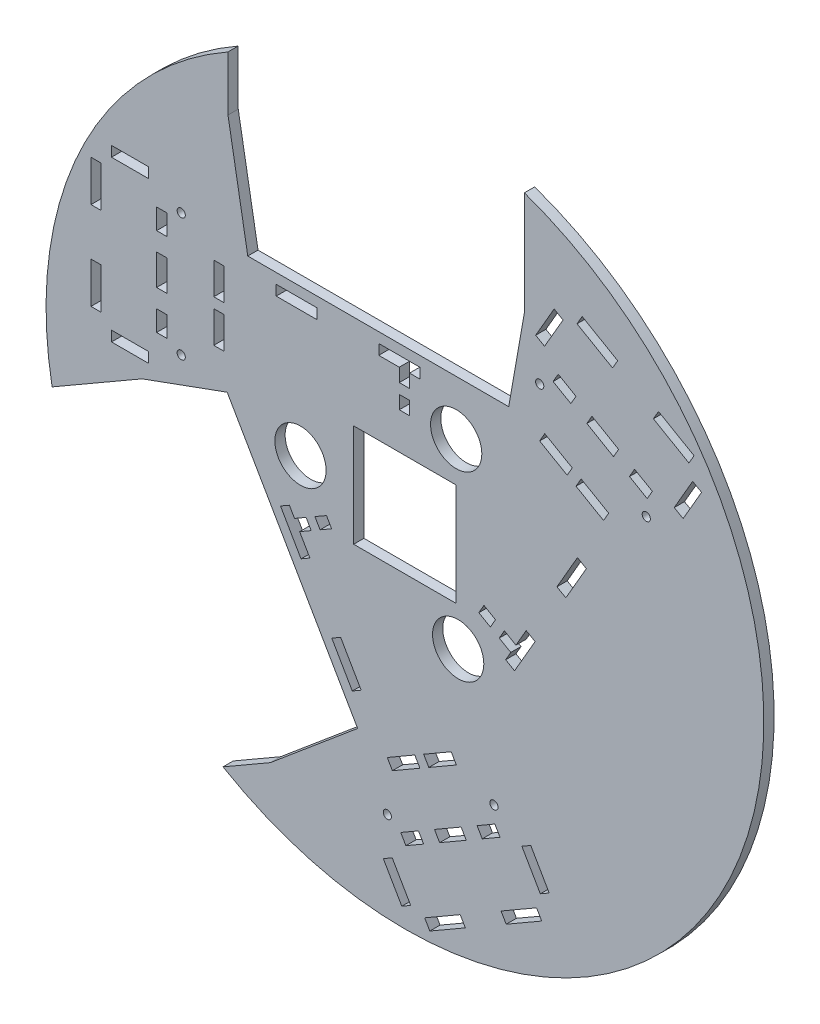
SolidWorks part; units mm, degrees
material "Balsa"
ref_plane "Plan de face" through (0, 0, 0) normal (0, 0, 1) x (1, 0, 0)
ref_plane "Plan de dessus" through (0, 0, 0) normal (0, 1, 0) x (1, 0, 0)
ref_plane "Plan de droite" through (0, 0, 0) normal (1, 0, 0) x (0, 0, -1)
sketch "Esquisse1" plane through (0, 0, 0) normal (0, 0, 1) x (1, 0, 0)
  circle A0 centre (148.0804, -12.1102) radius 175
  dimension "D1" = 350
extrude "Boss.-Extru.1" add sketch "Esquisse1" along normal blind 5
sketch "Esquisse2" plane through (0, 0, 5) normal (0, 0, 1) x (1, 0, 0)
  line L0 (135.3118, 53.7774) -> (135.3118, 48.7774)
  line L1 (5, 72.2774) -> (23, 72.2774)
  line L2 (5, 72.2774) -> (5, 67.2774)
  line L3 (5, 67.2774) -> (23, 67.2774)
  line L4 (23, 72.2774) -> (23, 67.2774)
  line L5 (-5, 62.2774) -> (0, 62.2774)
  line L6 (-5, 62.2774) -> (-5, 42.2774)
  line L7 (-5, 42.2774) -> (0, 42.2774)
  line L8 (0, 62.2774) -> (0, 42.2774)
  line L9 (-5, 19.2774) -> (0, 19.2774)
  line L10 (-5, 19.2774) -> (-5, -0.7226)
  line L11 (-5, -0.7226) -> (0, -0.7226)
  line L12 (0, 19.2774) -> (0, -0.7226)
  line L13 (5, -5.7226) -> (23, -5.7226)
  line L14 (5, -5.7226) -> (5, -10.7226)
  line L15 (5, -10.7226) -> (23, -10.7226)
  line L16 (23, -5.7226) -> (23, -10.7226)
  line L17 (27, 14.2774) -> (32, 14.2774)
  line L18 (27, 14.2774) -> (27, 4.2774)
  line L19 (27, 4.2774) -> (32, 4.2774)
  line L20 (32, 14.2774) -> (32, 4.2774)
  line L21 (27, 38.2774) -> (32, 38.2774)
  line L22 (27, 38.2774) -> (27, 23.2774)
  line L23 (27, 23.2774) -> (32, 23.2774)
  line L24 (32, 38.2774) -> (32, 23.2774)
  line L25 (27, 57.2774) -> (32, 57.2774)
  line L26 (27, 57.2774) -> (27, 47.2774)
  line L27 (27, 47.2774) -> (32, 47.2774)
  line L28 (32, 57.2774) -> (32, 47.2774)
  line L29 (54.86, 48.7774) -> (59.86, 48.7774)
  line L30 (54.86, 48.7774) -> (54.86, 33.2774)
  line L31 (54.86, 33.2774) -> (59.86, 33.2774)
  line L32 (59.86, 48.7774) -> (59.86, 33.2774)
  line L33 (54.86, 28.2774) -> (59.86, 28.2774)
  line L34 (54.86, 28.2774) -> (54.86, 12.7774)
  line L35 (54.86, 12.7774) -> (59.86, 12.7774)
  line L36 (59.86, 28.2774) -> (59.86, 12.7774)
  line L37 (85.3118, 53.7774) -> (105.3118, 53.7774)
  line L38 (85.3118, 53.7774) -> (85.3118, 48.7774)
  line L39 (85.3118, 48.7774) -> (105.3118, 48.7774)
  line L40 (105.3118, 53.7774) -> (105.3118, 48.7774)
  line L41 (145.3118, 37.2774) -> (150.3118, 37.2774)
  line L42 (145.3118, 37.2774) -> (145.3118, 30.7774)
  line L43 (145.3118, 30.7774) -> (150.3118, 30.7774)
  line L44 (150.3118, 37.2774) -> (150.3118, 30.7774)
  line L45 (135.3118, 48.7774) -> (145.3118, 48.7774)
  line L46 (155.3118, 48.7774) -> (135.3118, 48.7774) construction
  line L47 (145.3118, 48.7774) -> (145.3118, 42.2774)
  line L48 (145.3118, 42.2774) -> (150.3118, 42.2774)
  line L49 (150.3118, 42.2774) -> (150.3118, 48.7774)
  line L50 (150.3118, 48.7774) -> (155.3118, 48.7774)
  line L51 (155.3118, 48.7774) -> (155.3118, 53.7774)
  line L52 (155.3118, 53.7774) -> (135.3118, 53.7774)
  line L53 (292.7025, 69.6073) -> (283.7025, 54.0188)
  line L54 (292.7025, 69.6073) -> (288.3723, 72.1073)
  line L55 (288.3723, 72.1073) -> (279.3723, 56.5188)
  line L56 (283.7025, 54.0188) -> (279.3723, 56.5188)
  line L57 (289.0422, 83.2676) -> (286.5422, 78.9374)
  line L58 (289.0422, 83.2676) -> (271.7217, 93.2676)
  line L59 (271.7217, 93.2676) -> (269.2217, 88.9374)
  line L60 (286.5422, 78.9374) -> (269.2217, 88.9374)
  line L61 (251.8031, 104.7676) -> (249.3031, 100.4374)
  line L62 (251.8031, 104.7676) -> (234.4826, 114.7676)
  line L63 (234.4826, 114.7676) -> (231.9826, 110.4374)
  line L64 (249.3031, 100.4374) -> (231.9826, 110.4374)
  line L65 (225.1525, 108.6073) -> (216.1525, 93.0188)
  line L66 (225.1525, 108.6073) -> (220.8223, 111.1073)
  line L67 (220.8223, 111.1073) -> (211.8223, 95.5188)
  line L68 (216.1525, 93.0188) -> (211.8223, 95.5188)
  line L69 (231.473, 79.5547) -> (228.973, 75.2246)
  line L70 (231.473, 79.5547) -> (222.8127, 84.5547)
  line L71 (222.8127, 84.5547) -> (220.3127, 80.2246)
  line L72 (228.973, 75.2246) -> (220.3127, 80.2246)
  line L73 (252.2576, 67.5547) -> (249.7576, 63.2246)
  line L74 (252.2576, 67.5547) -> (239.2672, 75.0547)
  line L75 (239.2672, 75.0547) -> (236.7672, 70.7246)
  line L76 (249.7576, 63.2246) -> (236.7672, 70.7246)
  line L77 (268.7121, 58.0547) -> (266.2121, 53.7246)
  line L78 (268.7121, 58.0547) -> (260.0518, 63.0547)
  line L79 (260.0518, 63.0547) -> (257.5518, 58.7246)
  line L80 (266.2121, 53.7246) -> (257.5518, 58.7246)
  line L81 (247.4209, 38.1773) -> (244.9209, 33.8472)
  line L82 (247.4209, 38.1773) -> (233.9975, 45.9273)
  line L83 (233.9975, 45.9273) -> (231.4975, 41.5972)
  line L84 (244.9209, 33.8472) -> (231.4975, 41.5972)
  line L85 (229.6673, 48.4273) -> (227.1673, 44.0972)
  line L86 (229.6673, 48.4273) -> (216.2439, 56.1773)
  line L87 (216.2439, 56.1773) -> (213.7439, 51.8472)
  line L88 (227.1673, 44.0972) -> (213.7439, 51.8472)
  line L89 (211.5251, -33.996) -> (207.195, -31.496)
  line L90 (236.5251, 9.3053) -> (226.5251, -8.0153)
  line L91 (236.5251, 9.3053) -> (232.195, 11.8053)
  line L92 (232.195, 11.8053) -> (222.195, -5.5153)
  line L93 (226.5251, -8.0153) -> (222.195, -5.5153)
  line L94 (192.2357, -34.4063) -> (189.7357, -38.7364)
  line L95 (192.2357, -34.4063) -> (186.6065, -31.1563)
  line L96 (186.6065, -31.1563) -> (184.1065, -35.4864)
  line L97 (189.7357, -38.7364) -> (184.1065, -35.4864)
  line L98 (207.195, -31.496) -> (202.195, -40.1563)
  line L99 (202.195, -40.1563) -> (196.5658, -36.9063)
  line L100 (196.5658, -36.9063) -> (194.0658, -41.2364)
  line L101 (194.0658, -41.2364) -> (199.695, -44.4864)
  line L102 (199.695, -44.4864) -> (197.195, -48.8165)
  line L103 (197.195, -48.8165) -> (201.5251, -51.3165)
  line L104 (201.5251, -51.3165) -> (211.5251, -33.996)
  line L105 (146.5388, -178.2153) -> (137.5388, -162.6268)
  line L106 (146.5388, -178.2153) -> (150.869, -175.7153)
  line L107 (150.869, -175.7153) -> (141.869, -160.1268)
  line L108 (137.5388, -162.6268) -> (141.869, -160.1268)
  line L109 (160.1991, -181.8755) -> (157.6991, -177.5454)
  line L110 (160.1991, -181.8755) -> (177.5196, -171.8755)
  line L111 (177.5196, -171.8755) -> (175.0196, -167.5454)
  line L112 (157.6991, -177.5454) -> (175.0196, -167.5454)
  line L113 (197.4382, -160.3755) -> (194.9382, -156.0454)
  line L114 (197.4382, -160.3755) -> (214.7587, -150.3755)
  line L115 (214.7587, -150.3755) -> (212.2587, -146.0454)
  line L116 (194.9382, -156.0454) -> (212.2587, -146.0454)
  line L117 (214.0888, -139.2153) -> (205.0888, -123.6268)
  line L118 (214.0888, -139.2153) -> (218.4189, -136.7153)
  line L119 (218.4189, -136.7153) -> (209.4189, -121.1268)
  line L120 (205.0888, -123.6268) -> (209.4189, -121.1268)
  line L121 (185.7683, -130.1627) -> (183.2683, -125.8326)
  line L122 (185.7683, -130.1627) -> (194.4286, -125.1627)
  line L123 (194.4286, -125.1627) -> (191.9286, -120.8326)
  line L124 (183.2683, -125.8326) -> (191.9286, -120.8326)
  line L125 (164.9837, -142.1627) -> (162.4837, -137.8326)
  line L126 (164.9837, -142.1627) -> (177.9741, -134.6627)
  line L127 (177.9741, -134.6627) -> (175.4741, -130.3326)
  line L128 (162.4837, -137.8326) -> (175.4741, -130.3326)
  line L129 (148.5292, -151.6627) -> (146.0292, -147.3326)
  line L130 (148.5292, -151.6627) -> (157.1895, -146.6627)
  line L131 (157.1895, -146.6627) -> (154.6895, -142.3326)
  line L132 (146.0292, -147.3326) -> (154.6895, -142.3326)
  line L133 (141.9604, -123.2852) -> (139.4604, -118.9551)
  line L134 (141.9604, -123.2852) -> (155.3838, -115.5352)
  line L135 (155.3838, -115.5352) -> (152.8838, -111.2051)
  line L136 (139.4604, -118.9551) -> (152.8838, -111.2051)
  line L137 (159.7139, -113.0352) -> (157.2139, -108.7051)
  line L138 (159.7139, -113.0352) -> (173.1373, -105.2852)
  line L139 (173.1373, -105.2852) -> (170.6373, -100.9551)
  line L140 (157.2139, -108.7051) -> (170.6373, -100.9551)
  line L141 (97.4044, -56.1119) -> (101.7345, -53.6119)
  line L142 (122.4044, -99.4132) -> (112.4044, -82.0927)
  line L143 (122.4044, -99.4132) -> (126.7345, -96.9132)
  line L144 (126.7345, -96.9132) -> (116.7345, -79.5927)
  line L145 (112.4044, -82.0927) -> (116.7345, -79.5927)
  line L146 (106.6938, -39.2017) -> (104.1938, -34.8716)
  line L147 (106.6938, -39.2017) -> (112.323, -35.9517)
  line L148 (112.323, -35.9517) -> (109.823, -31.6216)
  line L149 (104.1938, -34.8716) -> (109.823, -31.6216)
  line L150 (101.7345, -53.6119) -> (96.7345, -44.9517)
  line L151 (96.7345, -44.9517) -> (102.3637, -41.7017)
  line L152 (102.3637, -41.7017) -> (99.8637, -37.3716)
  line L153 (99.8637, -37.3716) -> (94.2345, -40.6216)
  line L154 (94.2345, -40.6216) -> (91.7345, -36.2914)
  line L155 (91.7345, -36.2914) -> (87.4044, -38.7914)
  line L156 (87.4044, -38.7914) -> (97.4044, -56.1119)
  line L157 (135.3118, 53.7774) -> (135.3118, 48.7774) construction
  line L158 (105.3118, 53.7774) -> (135.3118, 53.7774) construction
  point P83 (148.0804, -12.1102)
  point P192 (148.0804, -12.1102)
  point P193 (148.0804, -12.1102)
  dimension "D1" = 3
extrude "Enlèv. mat.-Extru.1" cut sketch "Esquisse2" against normal blind 5
sketch "Esquisse6" plane through (0, 0, 5) normal (0, 0, 1) x (1, 0, 0)
  line L0 (93.9998, -7.2151) -> (100.2998, -18.127) construction
  line L1 (206.3213, 102.2219) -> (206.3213, 185.5637)
  line L2 (123.0804, -37.1102) -> (173.0804, -37.1102)
  line L3 (123.0804, -37.1102) -> (123.0804, 12.8898)
  line L4 (123.0804, 12.8898) -> (173.0804, 12.8898)
  line L5 (173.0804, -37.1102) -> (173.0804, 12.8898)
  line L6 (123.0804, -37.1102) -> (173.0804, 12.8898) construction
  line L7 (123.0804, 12.8898) -> (173.0804, -37.1102) construction
  line L8 (206.3213, 185.5637) -> (61.7972, 185.5637)
  line L9 (61.7972, 113.4862) -> (71.4438, 58.7774)
  line L10 (71.4438, 58.7774) -> (198.6608, 58.7774)
  line L11 (198.6608, 58.7774) -> (206.3213, 102.2219)
  line L12 (61.7972, 185.5637) -> (61.7972, 113.4862)
  line L13 (19.9456, -18.8381) -> (-52.2306, -60.5091)
  line L14 (-52.2306, -60.5091) -> (20.0314, -185.6706)
  line L15 (82.4524, -149.6318) -> (125.0083, -113.9232)
  line L16 (125.0083, -113.9232) -> (61.3998, -3.7501)
  line L17 (61.3998, -3.7501) -> (19.9456, -18.8381)
  line L18 (20.0314, -185.6706) -> (82.4524, -149.6318)
  line L19 (87.4044, -38.7914) -> (97.4044, -56.1119) construction
  circle A0 centre (173.06, 32.2774) radius 12.5
  circle A1 centre (174.0314, -55.9369) radius 12.5
  circle A2 centre (97.1498, -12.671) radius 12.5
  point P2 (148.0804, -12.1102)
  point P8 (148.0804, -12.1102)
  point P10 (148.0804, -12.1102)
  point P35 (148.0804, -12.1102)
  dimension "D2" = 25
  dimension "D3" = 50
  dimension "D4" = 50
  dimension "D5" = 70.8876
  dimension "D6" = 50.5804
  dimension "D7" = 127.217
  dimension "D8" = 100
  dimension "D9" = 100
  dimension "D10" = 54.7088
  dimension "D11" = 43.4444
  dimension "D1" = 3
  dimension "D12" = 2
extrude "Enlèv. mat.-Extru.6" cut sketch "Esquisse6" against normal blind 5
hole_wizard "Trous de centrage Ø4.0mm1" positions "Esquisse8" profile "Esquisse9" hole size "Ø4.0" standard "Ansi Metric" end condition through all
sketch "Esquisse8" plane through (148.0804, -12.1102, -78) normal (0, 0, -1) x (1, 0, 0)
  point P0 (65.7012, -88.0226)
  point P3 (117.6627, -58.0226)
  point P6 (-109.0804, -72.8876)
  point P9 (-109.0804, -12.8876)
  point P12 (-8.5823, 130.9102)
  point P15 (43.3792, 100.9102)
sketch "Esquisse9" plane through (213.7816, 75.9124, -78) normal (1, 0, 0) x (0, 1, 0)
  line L0 (0, 0) -> (0, 83)
  line L1 (0, 83) -> (2, 83)
  line L2 (2, 83) -> (2, 0)
  line L3 (2, 0) -> (0, 0)
  line L4 (0, -6.35) -> (0, 107.95) construction
  dimension "Diamètre du perçage jusqu'au prochain" = 4
  dimension "Profondeur du perçage jusqu'au prochain" = 83
